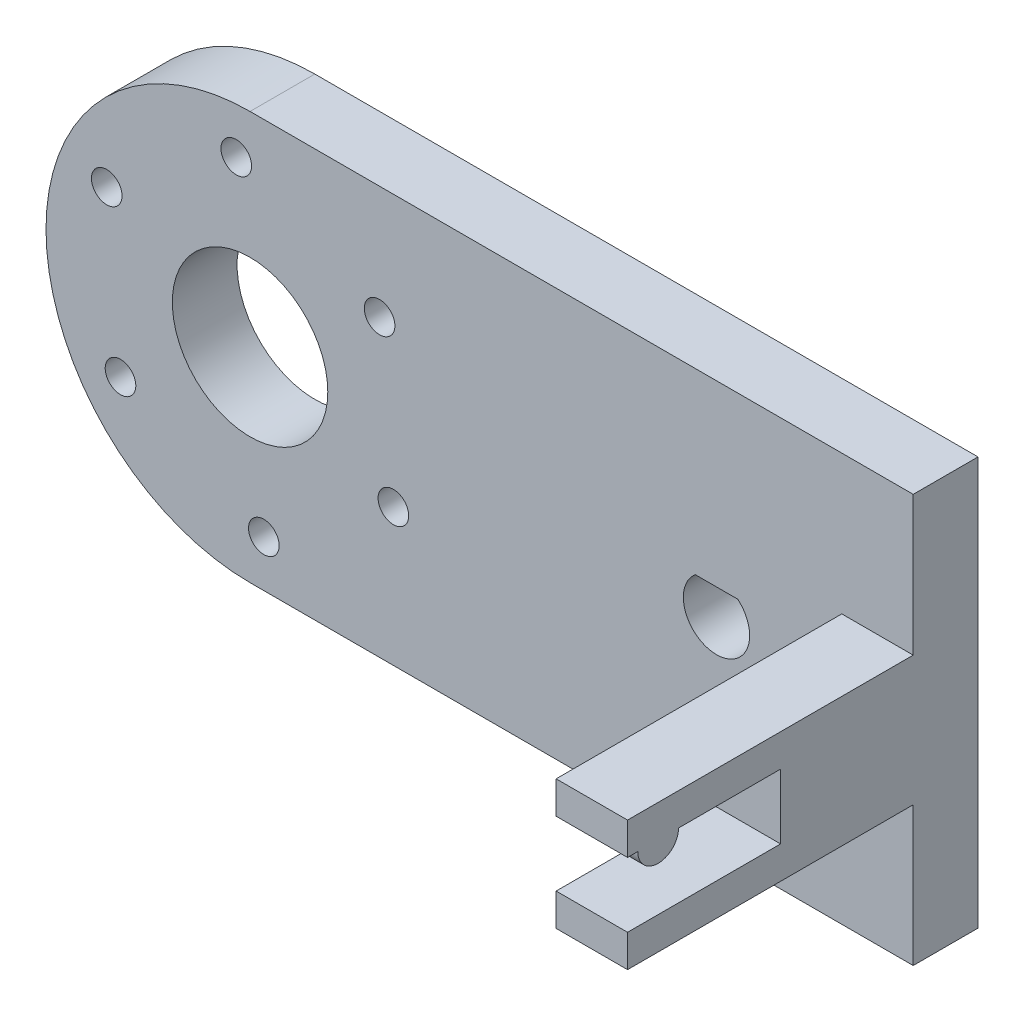
SolidWorks part; units mm, degrees
ref_plane "Front Plane" through (0, 0, 0) normal (0, 0, 1) x (1, 0, 0)
ref_plane "Top Plane" through (0, 0, 0) normal (0, 1, 0) x (1, 0, 0)
ref_plane "Right Plane" through (0, 0, 0) normal (1, 0, 0) x (0, 0, -1)
sketch "Sketch1" plane through (0, 0, 0) normal (0, 0, 1) x (1, 0, 0)
  line L1 (0, 20) -> (65, 20)
  line L2 (0, 20) -> (0, -20)
  line L3 (0, -20) -> (65, -20)
  line L4 (65, 20) -> (65, -20)
  circle A0 centre (0, 0) radius 20
  dimension "D1" = 40
  dimension "D2" = 65
extrude "Boss-Extrude1" add sketch "Sketch1" along normal blind 6.35 contours L2 L1 L4 L3 | A0
sketch "Sketch2" plane through (0, 0, 6.35) normal (0, 0, 1) x (1, 0, 0)
  line L0 (0, 0) -> (0, 15.5) construction
  line L1 (0, 0) -> (-1.3509, 15.441) construction
  line L2 (0, 0) -> (1.3509, -15.441) construction
  circle A0 centre (0, 0) radius 7.62
  circle A1 centre (0, 0) radius 15.5 construction
  circle A2 centre (-1.3509, 15.441) radius 1.5
  circle A3 centre (12.6969, 8.8904) radius 1.5
  circle A4 centre (14.0478, -6.5506) radius 1.5
  circle A5 centre (1.3509, -15.441) radius 1.5
  circle A6 centre (-12.6969, -8.8904) radius 1.5
  circle A7 centre (-14.0478, 6.5506) radius 1.5
  point P20 (0, 0)
  dimension "D1" = 15.24
  dimension "D2" = 31
  dimension "D4" = 3
  dimension "D3" = 5
  dimension "D5" = 6
extrude "Cut-Extrude1" cut sketch "Sketch2" against normal through all
ref_plane "Plane1" through (0, 0, 0) normal (0, 1, 0) x (1, 0, 0)
sketch "Sketch4" plane through (0, 0, 0) normal (0, 1, 0) x (1, 0, 0)
  line L1 (65, -6.35) -> (58, -6.35)
  line L2 (65, -6.35) -> (65, -34.35)
  line L3 (65, -34.35) -> (58, -34.35)
  line L4 (58, -6.35) -> (58, -34.35)
  dimension "D1" = 7
  dimension "D2" = 28
extrude "Boss-Extrude2" add sketch "Sketch4" along normal mid plane 12.7
sketch "Sketch5" plane through (65, 0, 0) normal (1, 0, 0) x (0, 0, -1)
  line L0 (-34.35, 6.35) -> (-34.35, -6.35) construction
  line L1 (-34.35, 3.175) -> (-19.35, 3.175)
  line L2 (-34.35, 3.175) -> (-34.35, -3.175)
  line L3 (-34.35, -3.175) -> (-19.35, -3.175)
  line L4 (-19.35, 3.175) -> (-19.35, -3.175)
  line L5 (0, 0) -> (-34.35, 0) construction
  line L6 (20.3625, 0) -> (-20.3625, 0) construction
  point P11 (-19.35, 0)
  dimension "D1" = 6.35
  dimension "D2" = 15
extrude "Cut-Extrude2" cut sketch "Sketch5" against normal up to next
sketch "Sketch6" plane through (0, 0, 0) normal (0, 0, -1) x (-1, 0, 0)
  line L0 (-65, 0) -> (0, 0) construction
  line L1 (-65, 20) -> (-65, -20) construction
  line L2 (-47.7967, 2.5) -> (-43.6433, 2.5)
  arc A0 (-47.7967, 2.5) -> (-43.6433, 2.5) centre (-45.72, 0) ccw
  point P9 (-45.72, -3.25)
  dimension "D1" = 6.5
  dimension "D2" = 45.72
  dimension "D3" = 5.75
extrude "Cut-Extrude3" cut sketch "Sketch6" against normal up to next
sketch "Sketch7" plane through (0, 0, 0) normal (0, 0, -1) x (-1, 0, 0)
  line L0 (-45.72, 13.5) -> (-45.72, 17.5) construction
  circle A0 centre (-45.72, 0) radius 15.5 construction
  arc A1 (-47.7967, 2.5) -> (-43.6433, 2.5) centre (-45.72, 0) ccw construction
  circle A2 centre (-45.72, 0) radius 13.5
  circle A3 centre (-45.72, 0) radius 17.5
  point P9 (-45.72, 15.5)
  dimension "D1" = 31
  dimension "D2" = 4
extrude "Cut-Extrude4" cut sketch "Sketch7" against normal blind 2
sketch "Sketch8" plane through (65, 0, 0) normal (1, 0, 0) x (0, 0, -1)
  line L0 (-19.35, 3.175) -> (-34.35, 3.175) construction
  line L2 (-34.35, 6.35) -> (-34.35, 3.175) construction
  circle A0 centre (-31.35, 3.175) radius 2
  point P5 (-31.9021, 3.5)
  dimension "D1" = 4
  dimension "D2" = 3
extrude "Boss-Extrude3" add sketch "Sketch8" against normal up to surface (7 mm away) up to face at (58, 0, 23.6)
